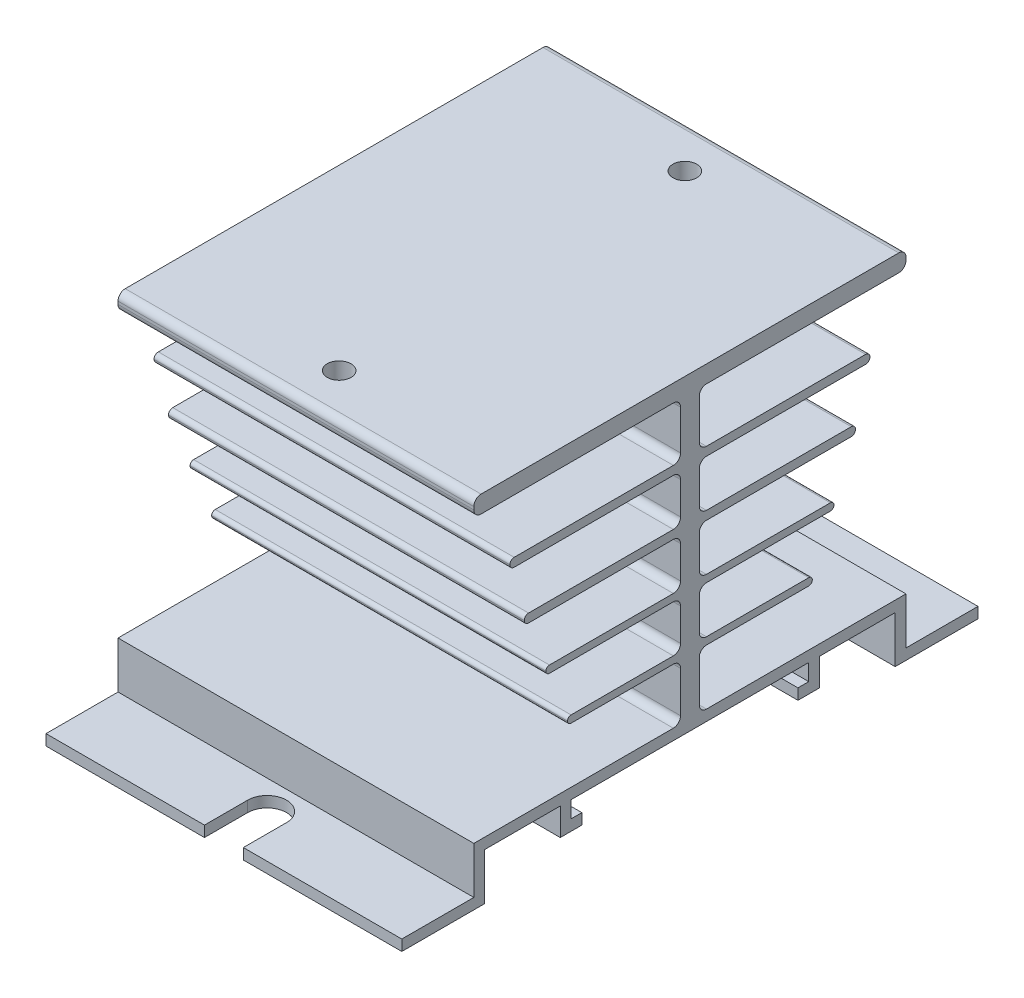
SolidWorks part; units mm, degrees
material "6061 Alloy"
ref_plane "Front Plane" through (0, 0, 0) normal (0, 0, 1) x (1, 0, 0)
ref_plane "Top Plane" through (0, 0, 0) normal (0, 1, 0) x (1, 0, 0)
ref_plane "Right Plane" through (0, 0, 0) normal (1, 0, 0) x (0, 0, -1)
sketch "BaseS" plane through (0, 0, 0) normal (1, 0, 0) x (0, 0, -1)
  line L0 (30, 0) -> (-30, 0)
  line L1 (-30, 0) -> (-30, -6.5)
  line L2 (-30, -6.5) -> (-40, -6.5)
  line L3 (30, 0) -> (30, -6.5)
  line L4 (30, -6.5) -> (40, -6.5)
  dimension "LegLength" = 10
  dimension "LegHeight" = 6.5
  dimension "BaseLength" = 80
  dimension "RefMainBaseLength" = 60
extrude "Base" add sketch "BaseS" along normal mid plane 49.4 thin thin type one direction reverse wall 1.5
sketch "DinRailLegS" plane through (0, 0, 0) normal (1, 0, 0) x (0, 0, -1)
  line L0 (18, -1.5) -> (18, -5.3)
  line L1 (18, -5.3) -> (15, -5.3)
  line L2 (28.5, -1.5) -> (-28.5, -1.5) construction
  dimension "D1" = 18
  dimension "Height" = 3.8
  dimension "Length" = 3
extrude "DinRailLeg" add sketch "DinRailLegS" along normal up to surface (24.7 mm away) and the other way up to surface (24.7 mm away) thin up to face at (24.7, -5.0833, 0) other way up to face at (-24.7, -5.0833, 0) thin type one direction wall 1.5
sketch "MainRibS" plane through (0, 0, 0) normal (1, 0, 0) x (0, 0, -1)
  line L0 (0, 0) -> (0, 41.5)
  dimension "Height" = 41.5
extrude "MainRib" add sketch "MainRibS" along normal up to surface (24.7 mm away) and the other way up to surface (24.7 mm away) thin up to face at (24.7, -4.5667, -5.5) other way up to face at (-24.7, -4.5667, -5.5) thin type mid plane wall 2.6
sketch "TopBaseS" plane through (0, 0, 0) normal (1, 0, 0) x (0, 0, -1)
  line L0 (-30, 41.5) -> (30, 41.5)
  line L1 (1.3, 41.5) -> (-1.3, 41.5) construction
  line L2 (-30, 0) -> (-30, -6.5) construction
  point P4 (0, 41.5)
extrude "TopBase" add sketch "TopBaseS" along normal up to surface (24.7 mm away) and the other way up to surface (24.7 mm away) thin up to face at (24.7, 0.0364, -4.5) other way up to face at (-24.7, 0.0364, -4.5) thin type one direction wall 2.4
sketch "Rib1S" plane through (0, 0, 0) normal (1, 0, 0) x (0, 0, -1)
  line L0 (25, 31.6) -> (-25, 31.6)
  line L1 (-1.3, 39.1) -> (-30, 39.1) construction
  line L3 (0, 27.17) -> (0, -27.17) construction
  point P5 (0, 31.6)
  dimension "Height" = 7.5
  dimension "WidthControl" = 5
  dimension "RefWidth" = 50
extrude "Rib1" add sketch "Rib1S" along normal up to surface (24.7 mm away) and the other way up to surface (24.7 mm away) thin up to face at (24.7, 6.0462, -3.8077) other way up to face at (-24.7, 6.0462, -3.8077) thin type one direction reverse wall 1.2
sketch "Rib2S" plane through (0, 0, 0) normal (1, 0, 0) x (0, 0, -1)
  line L0 (23, 23.9) -> (-23, 23.9)
  line L1 (0, 27.17) -> (0, -27.17) construction
  line L2 (-25, 30.4) -> (-1.3, 30.4) construction
  line L3 (-25, 31.6) -> (-25, 30.4) construction
  point P2 (0, 23.9)
  dimension "H" = 6.5
  dimension "WC" = 2
  dimension "RefW" = 46
extrude "Rib2" add sketch "Rib2S" against normal up to surface (24.7 mm away) and the other way up to surface (24.7 mm away) thin up to face at (-24.7, 11.9176, -2.9118) other way up to face at (24.7, 11.9176, -2.9118) thin type one direction reverse wall 1.2
sketch "Rib3S" plane through (0, 0, 0) normal (1, 0, 0) x (0, 0, -1)
  line L0 (-20, 16.2) -> (20, 16.2)
  line L1 (0, 27.17) -> (0, -27.17) construction
  line L2 (-23, 22.7) -> (-1.3, 22.7) construction
  line L3 (-23, 23.9) -> (-23, 22.7) construction
  point P2 (0, 16.2)
  dimension "H" = 6.5
  dimension "WC" = 3
  dimension "RefW" = 40
extrude "Rib3" add sketch "Rib3S" along normal up to surface (24.7 mm away) and the other way up to surface (24.7 mm away) thin up to face at (24.7, 14.0857, -2.3571) other way up to face at (-24.7, 14.0857, -2.3571) thin type one direction wall 1
sketch "Rib4S" plane through (0, 0, 0) normal (1, 0, 0) x (0, 0, -1)
  line L0 (-17, 8.7) -> (17, 8.7)
  line L1 (0, 27.17) -> (0, -27.17) construction
  line L2 (-1.3, 15.2) -> (-20, 15.2) construction
  line L3 (-20, 16.2) -> (-20, 15.2) construction
  point P2 (0, 8.7)
  dimension "H" = 6.5
  dimension "WC" = 3
  dimension "RefW" = 34
extrude "Rib4" add sketch "Rib4S" along normal up to surface (24.7 mm away) and the other way up to surface (24.7 mm away) thin up to face at (24.7, 14.344, -1.98) other way up to face at (-24.7, 14.344, -1.98) thin type one direction wall 1
sketch "MountingSlotS" plane through (0, -6.5, 0) normal (0, 1, 0) x (1, 0, 0)
  line L0 (0, 40) -> (0, 34) construction
  line L1 (24.7, 40) -> (-24.7, 40) construction
  line L2 (2.7, 40) -> (2.7, 34)
  line L3 (-2.7, 40) -> (-2.7, 34)
  arc A0 (2.7, 40) -> (-2.7, 40) centre (0, 40) ccw
  arc A1 (-2.7, 34) -> (2.7, 34) centre (0, 34) ccw
  point P5 (0, 37)
  dimension "Height" = 6
  dimension "Width" = 5.4
extrude "MountingSlot" cut sketch "MountingSlotS" against normal through all
hole_wizard "M4x0.7 Tapped Hole1" positions "Sketch10" profile "Sketch11" tap size "M4x0.7" standard "ANSI Metric" end condition up to next
sketch "Sketch10" plane through (0, 41.5, 0) normal (0, 1, 0) x (1, 0, 0)
  line L0 (0, 30) -> (0, 24) construction
  line L1 (24.7, 30) -> (-24.7, 30) construction
  point P0 (0, 24)
  dimension "YDim" = 6
  dimension "D2" = 24
sketch "Sketch11" plane through (0, 41.5, -24) normal (1, 0, 0) x (0, 0, 1)
  line L0 (0, 0) -> (0, 11.1)
  line L1 (0, 11.1) -> (1.65, 11.1)
  line L2 (1.65, 11.1) -> (1.65, 0)
  line L5 (1.65, 0) -> (0, 0)
  line L11 (0, -6.35) -> (0, 107.95) construction
  dimension "Thru Tap Drill Dia." = 3.3
  dimension "Thru Tap Drill Depth" = 11.1
cosmetic thread "Hole Thread1" parameters "D2"=4
mirror "Mounting Features VM" about plane through (0, 0, 0) normal (0, 0, 1) of "DinRailLeg", "M4x0.7 Tapped Hole1", "MountingSlot"
fillet "TBF" radius 1 4 edges at (0, 39.1, -30) (0, 41.5, -30) (0, 39.1, 30) (0, 41.5, 30)
fillet "MRF" radius 1 20 edges at (0, 15.2, 1.3) (0, 22.7, -1.3) (0, 15.2, -1.3) (0, 7.7, -1.3) (0, 7.7, 1.3) (0, 22.7, 1.3) (0, 16.2, -1.3) (0, 8.7, -1.3) (0, 0, -1.3) (0, 0, 1.3) (0, 8.7, 1.3) (0, 16.2, 1.3) (0, 23.9, 1.3) (0, 30.4, 1.3) (0, 30.4, -1.3) (0, 23.9, -1.3) (0, 31.6, -1.3) (0, 31.6, 1.3) (0, 39.1, 1.3) (0, 39.1, -1.3)
fillet "F1" radius 0.6 4 edges at (0, 30.4, -25) (0, 31.6, -25) (0, 30.4, 25) (0, 31.6, 25)
fillet "F2" radius 0.6 4 edges at (0, 23.9, -23) (0, 22.7, -23) (0, 23.9, 23) (0, 22.7, 23)
fillet "F3" radius 0.5 4 edges at (0, 15.2, -20) (0, 16.2, -20) (0, 15.2, 20) (0, 16.2, 20)
fillet "F4" radius 0.5 4 edges at (0, 8.7, 17) (0, 7.7, 17) (0, 7.7, -17) (0, 8.7, -17)
